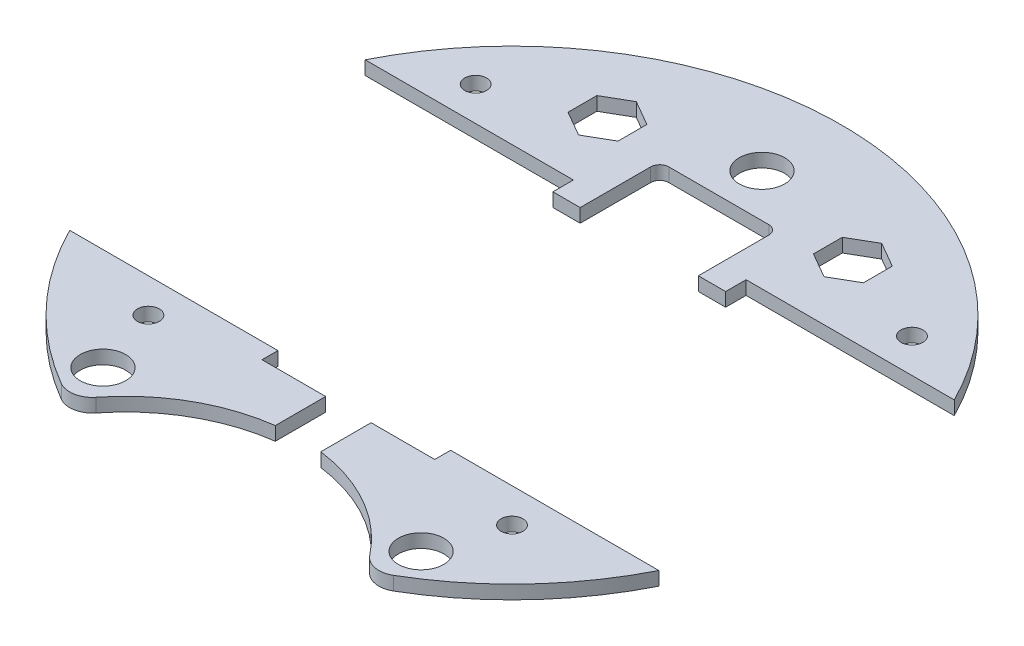
SolidWorks part; units mm, degrees
material "Acrylic (Medium-high impact)"
ref_plane "Front Plane" through (0, 0, 0) normal (0, 0, 1) x (1, 0, 0)
ref_plane "Top Plane" through (0, 0, 0) normal (0, 1, 0) x (1, 0, 0)
ref_plane "Right Plane" through (0, 0, 0) normal (1, 0, 0) x (0, 0, -1)
sketch "Sketch1" plane through (0, 0, 0) normal (0, 1, 0) x (1, 0, 0)
  line L0 (0, -85) -> (-32.4891, -64.8129) construction
  line L1 (0, -85) -> (0, 0) construction
  arc A0 (36.5434, -62.6165) -> (-36.5434, -62.6165) centre (0, 0) ccw
  arc A1 (30.0898, -61.3851) -> (-30.0898, -61.3851) centre (0, -85) ccw
  arc A2 (36.5434, -62.6165) -> (30.0898, -61.3851) centre (34.0231, -58.2982) cw
  arc A3 (-30.0898, -61.3851) -> (-36.5434, -62.6165) centre (-34.0231, -58.2982) cw
  dimension "D1" = 145
  dimension "D2" = 76.5
  dimension "D4" = 5
  dimension "D3" = 85
extrude "Boss-Extrude1" add sketch "Sketch1" along normal blind 3
sketch "solenoid placement" plane through (0, 3, 0) normal (0, 1, 0) x (1, 0, 0)
  line L4 (-19, -36) -> (19, -36)
  line L5 (-19, 28) -> (-19, -36)
  line L6 (19, 28) -> (-19, 28)
  line L7 (19, -36) -> (19, 28)
  line L8 (-19, -36) -> (19, -36)
  line L9 (-19, 28) -> (-19, -36)
  line L10 (19, 28) -> (-19, 28)
  line L11 (19, -36) -> (19, 28)
  dimension "D1" = 0
extrude "Cut-Extrude1" cut sketch "solenoid placement" against normal through all
sketch "Sketch4" plane through (0, 3, 0) normal (0, 1, 0) x (1, 0, 0)
  line L6 (19, 28) -> (-19, 28) construction
  line L10 (-13, 28) -> (13, 28)
  line L11 (13, 28) -> (13, 43.5)
  line L12 (11, 45.5) -> (-11, 45.5)
  line L13 (-13, 43.5) -> (-13, 28)
  arc A5 (13, 43.5) -> (11, 45.5) centre (11, 43.5) ccw
  arc A7 (-11, 45.5) -> (-13, 43.5) centre (-11, 43.5) ccw
  point P10 (0, 28)
  point P11 (0, 28)
  dimension "D3" = 2
  dimension "D1" = 26
  dimension "D2" = 17.5
extrude "Cut-Extrude4" cut sketch "Sketch4" against normal through all
sketch "Sketch5" plane through (0, 3, 0) normal (0, 1, 0) x (1, 0, 0)
  line L6 (0, 0) -> (0, 72.5) construction
  line L7 (-21.5, 51.1754) -> (-27, 54.3509)
  line L8 (-27, 54.3509) -> (-32.5, 51.1754)
  line L9 (-32.5, 51.1754) -> (-32.5, 44.8246)
  line L10 (-32.5, 44.8246) -> (-27, 41.6491)
  line L11 (-27, 41.6491) -> (-21.5, 44.8246)
  line L12 (-21.5, 44.8246) -> (-21.5, 51.1754)
  line L13 (21.5, 44.8246) -> (21.5, 51.1754)
  line L14 (27, 41.6491) -> (21.5, 44.8246)
  line L15 (32.5, 44.8246) -> (27, 41.6491)
  line L16 (32.5, 51.1754) -> (32.5, 44.8246)
  line L17 (27, 54.3509) -> (32.5, 51.1754)
  line L18 (21.5, 51.1754) -> (27, 54.3509)
  circle A0 centre (-27, 48) radius 5.5 construction
  arc A1 (36.5434, -62.6165) -> (-36.5434, -62.6165) centre (0, 0) ccw construction
  circle A2 centre (27, 48) radius 5.5 construction
  dimension "D1" = 11
extrude "Cut-Extrude5" cut sketch "Sketch5" against normal through all
sketch "Sketch6" plane through (0, 3, 0) normal (0, 1, 0) x (1, 0, 0)
  circle A1 centre (40, -40) radius 2.4
  circle A2 centre (40, -40) radius 2.4
  circle A3 centre (-40, -40) radius 2.4
  circle A4 centre (-40, -40) radius 2.4
  circle A5 centre (48, 40) radius 2.4
  circle A6 centre (48, 40) radius 2.4
  circle A7 centre (-48, 40) radius 2.4
  circle A8 centre (-48, 40) radius 2.4
  dimension "D1" = 0
  dimension "D2" = 0
  dimension "D3" = 0
  dimension "D4" = 0
extrude "Cut-Extrude6" cut sketch "Sketch6" against normal through all
sketch "Sketch3" plane through (0, 3, 0) normal (0, 1, 0) x (1, 0, 0)
  line L0 (-19, 28) -> (-19, 32.5)
  line L1 (72.5, -32.5) -> (-72.5, -32.5)
  line L2 (72.5, -32.5) -> (72.5, 32.5)
  line L3 (72.5, 32.5) -> (19, 32.5)
  line L4 (-72.5, -32.5) -> (-72.5, 32.5)
  line L5 (72.5, -32.5) -> (-72.5, 32.5) construction
  line L6 (72.5, 32.5) -> (-72.5, -32.5) construction
  line L7 (-19, 28) -> (19, 28)
  line L8 (19, 28) -> (19, 32.5)
  line L9 (-19, 32.5) -> (-72.5, 32.5)
  arc A0 (36.5434, -62.6165) -> (-36.5434, -62.6165) centre (0, 0) ccw construction
  point P0 (0, 0)
  dimension "D1" = 65
extrude "Cut-Extrude3" cut sketch "Sketch3" against normal through all
sketch "Sketch7" plane through (0, 3, 0) normal (0, 1, 0) x (1, 0, 0)
  line L5 (-5, 0) -> (5, 0)
  line L6 (-5, 0) -> (-5, -50)
  line L7 (-5, -50) -> (5, -50)
  line L8 (5, 0) -> (5, -50)
  point P4 (0, 0)
  dimension "D1" = 10
  dimension "D2" = 50
extrude "Cut-Extrude7" cut sketch "Sketch7" against normal through all
sketch "Sketch9" plane through (0, 3, 0) normal (0, -1, 0) x (1, 0, 0)
  circle A1 centre (35, 55) radius 5
  circle A2 centre (35, 55) radius 5
  circle A3 centre (-35, 55) radius 5
  circle A4 centre (-35, 55) radius 5
  dimension "D1" = 0
  dimension "D2" = 0
extrude "Cut-Extrude11" cut sketch "Sketch9" along normal through all
sketch "Sketch10" plane through (0, 3, 0) normal (0, 1, 0) x (1, 0, 0)
  circle A1 centre (0, 55) radius 5
  circle A2 centre (0, 55) radius 5
  dimension "D1" = 0
extrude "Cut-Extrude12" cut sketch "Sketch10" against normal through all and the other way through all
equation "\"smallPulleyTeeth\"= 30"
equation "\"largePulleyTeeth\"= 30"
equation "\"eighthThick\"= 3.0mm"
equation "\"sixteenthThick\"= 1.7mm"
equation "\"quarterThick\"=6.0mm"
equation "\"OD\"= 145mm"
equation "\"puckAngle\"= 60.5deg"
equation "\"D1@Sketch1\"=\"OD\""
equation "\"puckDiam\"= 76.5mm"
equation "\"D2@Sketch1\"=\"puckDiam\""
equation "\"D1@Boss-Extrude1\"=\"eighthThick\""
equation "\"axlePress\"= 5.9mm"
equation "\"press\"= 0.2mm"
equation "\"wheelClear\"= 0.3mm"
equation "\"10-32clear\"= 4.8mm"
equation "\"6-32clear\"= 3.3mm"
equation "\"8-32clear\"= 4.0mm"
equation "\"wheelHeight\"= 22mm"
equation "\"wheelWell\"= 65mm"
equation "\"D1@Sketch3\"=\"wheelWell\""
equation "\"puckDist\"= 85mm"
equation "\"scoopFillet\"= 5mm"
equation "\"4-40clear\"= 3.0mm"
equation "\"D3@Sketch1\"=\"puckDist\""
equation "\"D4@Sketch1\"=\"scoopFillet\""
